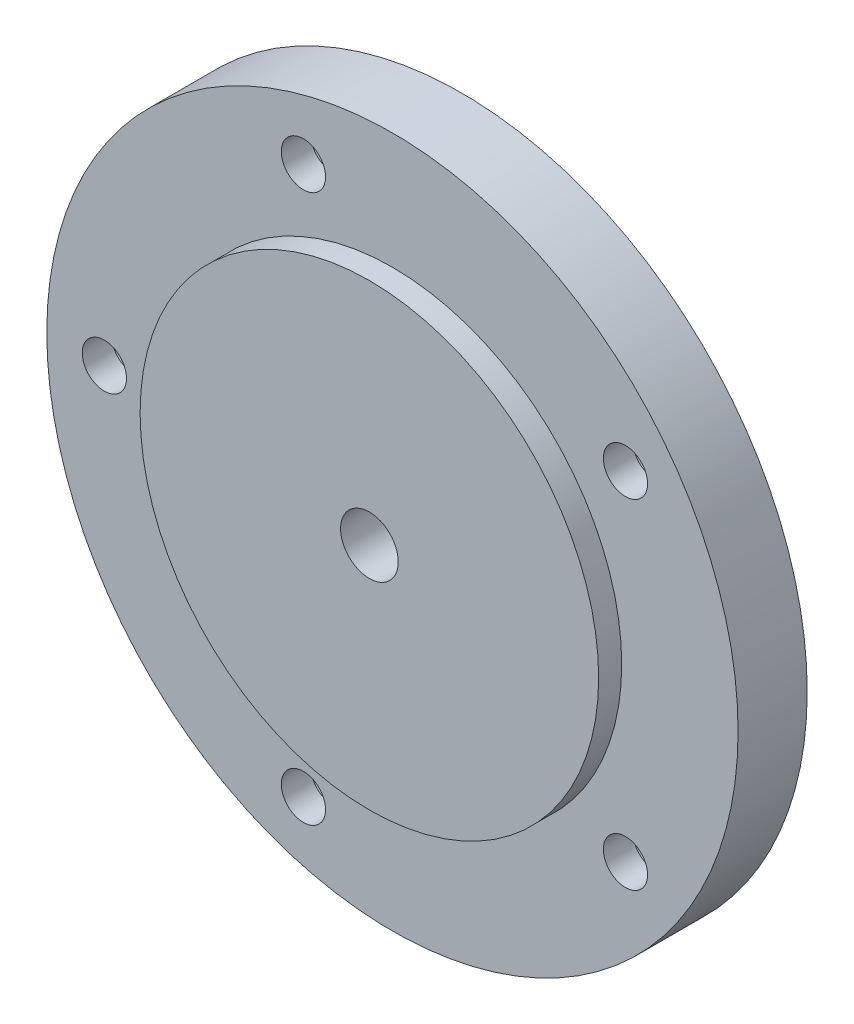
SolidWorks part; units mm, degrees
ref_plane "Front Plane" through (0, 0, 0) normal (0, 0, 1) x (1, 0, 0)
ref_plane "Top Plane" through (0, 0, 0) normal (0, 1, 0) x (1, 0, 0)
ref_plane "Right Plane" through (0, 0, 0) normal (1, 0, 0) x (0, 0, -1)
sketch "Sketch1" plane through (0, 0, 0) normal (0, 0, 1) x (1, 0, 0)
  circle A0 centre (0, 0) radius 19.05
  dimension "D1" = 38.1
extrude "Boss-Extrude1" add sketch "Sketch1" along normal blind 3.81
sketch "Sketch2" plane through (0, 0, 3.81) normal (0, 0, 1) x (1, 0, 0)
  circle A0 centre (0, 0) radius 12.6365
  dimension "D1" = 25.273
extrude "Boss-Extrude2" add sketch "Sketch2" along normal blind 1.27
sketch "Sketch4" plane through (0, 0, 0) normal (0, 0, -1) x (-1, 0, 0)
  circle A0 centre (0, 0) radius 15.875
  point P3 (15.875, 0)
  dimension "D1" = 31.75
hole_wizard "CBORE for #2 Socket Head Cap Screw1" positions "Sketch6" profile "Sketch5" counterbore size "#2" standard "ANSI Inch" end condition through all
sketch "Sketch6" plane through (0, 0, 0) normal (0, 0, -1) x (-1, 0, 0)
  point P0 (15.875, 0)
sketch "Sketch5" plane through (-15.875, 0, 0) normal (1, 0, 0) x (0, 1, 0)
  line L0 (0, 0) -> (0, 5.08)
  line L1 (0, 5.08) -> (1.2192, 5.08)
  line L3 (1.2192, 5.08) -> (1.2192, 2.1844)
  line L4 (1.2192, 2.1844) -> (2.3812, 2.1844)
  line L5 (2.3812, 2.1844) -> (2.3812, 0)
  line L7 (2.3812, 0) -> (0, 0)
  line L11 (0, -6.35) -> (0, 107.95) construction
  dimension "Thru Hole Dia." = 2.4384
  dimension "Thru Hole Depth" = 5.08
  dimension "C'Bore Dia." = 4.7625
  dimension "C'Bore Depth" = 2.1844
ref_axis "Axis1" through (0, 0, 0) along (0, 0, -1)
pattern_circular "CirPattern1" count 5 every 72 about axis through (0, 0, 0) along (0, 0, -1) of "CBORE for #2 Socket Head Cap Screw1"
sketch "Sketch7" plane through (0, 0, 0) normal (0, 0, -1) x (-1, 0, 0)
  point P0 (0, 0)
hole_wizard "1/8 (0.1250) Dowel Hole1" positions "Sketch9" profile "Sketch8" hole size "1/8" standard "ANSI Inch" end condition through all
sketch "Sketch9" plane through (0, 0, 0) normal (0, 0, -1) x (-1, 0, 0)
  point P0 (0, 0)
sketch "Sketch8" plane through (0, 0, 0) normal (1, 0, 0) x (0, 1, 0)
  line L0 (0, 0) -> (0, 5.08)
  line L1 (0, 5.08) -> (1.5875, 5.08)
  line L2 (1.5875, 5.08) -> (1.5875, 0)
  line L5 (1.5875, 0) -> (0, 0)
  line L11 (0, -6.35) -> (0, 107.95) construction
  dimension "Thru Hole Dia." = 3.175
  dimension "Thru Hole Depth" = 5.08
